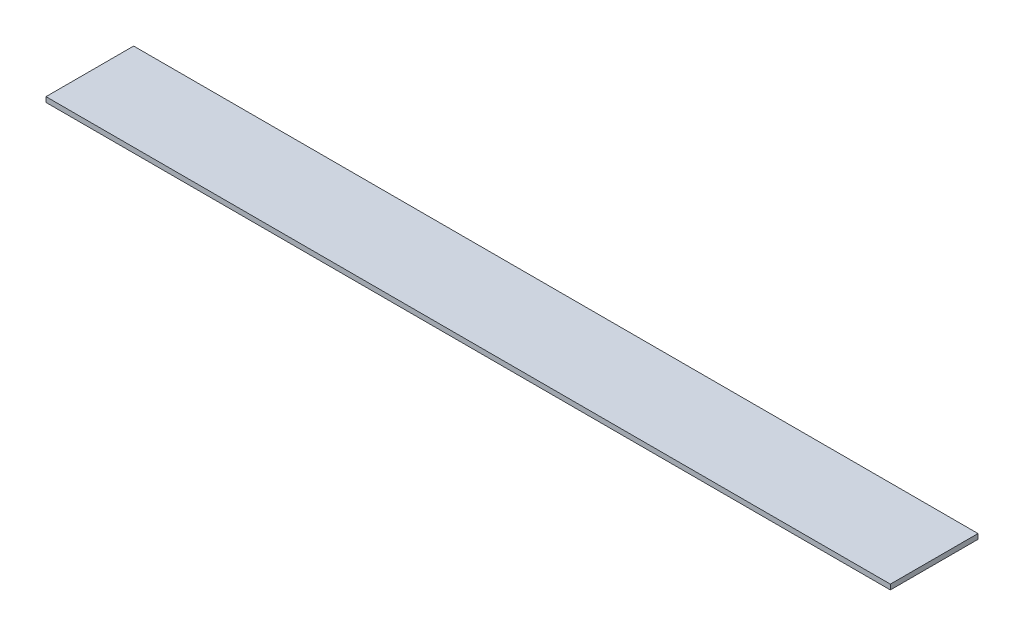
SolidWorks part; units mm, degrees
ref_plane "Front Plane" through (0, 0, 0) normal (0, 0, 1) x (1, 0, 0)
ref_plane "Top Plane" through (0, 0, 0) normal (0, 1, 0) x (1, 0, 0)
ref_plane "Right Plane" through (0, 0, 0) normal (1, 0, 0) x (0, 0, -1)
sketch "Sketch1" plane through (32.3643, 0, 0) normal (1, 0, 0) x (0, 0, -1)
  line L1 (-7.8759, 29.8822) -> (-7.8759, 35.6922) construction
  line L2 (-3.5343, 35.5407) -> (-4.9959, 34.0792)
  line L4 (-4.9959, 34.0792) -> (-4.9959, 33.9551)
  line L5 (-4.9959, 33.9551) -> (-2.3859, 33.9551)
  line L6 (-2.3859, 33.9551) -> (-2.3859, 32.3299)
  line L7 (-2.3859, 32.3299) -> (-5.5407, 29.1751)
  line L8 (-5.5407, 29.1751) -> (-10.2111, 29.1751)
  line L9 (-10.2111, 29.1751) -> (-13.3659, 32.3299)
  line L10 (-13.3659, 32.3299) -> (-13.3659, 33.9551)
  line L11 (-13.3659, 33.9551) -> (-10.7559, 33.9551)
  line L12 (-10.7559, 33.9551) -> (-10.7559, 34.0792)
  line L13 (-10.7559, 34.0792) -> (-12.2174, 35.5407)
  line L14 (-13.3659, 33.9551) -> (-2.9859, 33.9551)
  line L15 (-13.3659, 33.9551) -> (-13.3659, 33.3551)
  line L16 (-13.3659, 33.3551) -> (-2.9859, 33.3551)
  line L17 (-2.9859, 33.9551) -> (-2.9859, 33.3551)
  line L52 (-5.5365, 22.3651) -> (-2.3759, 19.2044)
  line L53 (-2.3759, 19.2044) -> (-2.3759, 17.5651)
  line L54 (-2.3759, 17.5651) -> (-4.9859, 17.5651)
  line L55 (-4.9859, 17.5651) -> (-4.9859, 17.4551)
  line L56 (-4.9859, 17.4551) -> (-3.5273, 15.9964)
  line L57 (-2.9686, 15.7651) -> (0.6241, 15.7651)
  line L58 (2.1241, 17.2651) -> (2.1241, 20.8578)
  line L59 (1.8927, 21.4164) -> (0.4341, 22.8751)
  line L60 (0.4341, 22.8751) -> (0.3241, 22.8751)
  line L61 (0.3241, 22.8751) -> (0.3241, 20.2651)
  line L62 (0.3241, 20.2651) -> (-1.3152, 20.2651)
  line L63 (-1.3152, 20.2651) -> (-4.4759, 23.4257)
  line L64 (-4.4759, 23.4257) -> (-4.4759, 28.1044)
  line L65 (-4.4759, 28.1044) -> (-1.3152, 31.2651)
  line L66 (-1.3152, 31.2651) -> (0.3241, 31.2651)
  line L67 (0.3241, 31.2651) -> (0.3241, 28.6551)
  line L68 (0.3241, 28.6551) -> (0.4341, 28.6551)
  line L69 (0.4341, 28.6551) -> (1.8927, 30.1137)
  line L70 (2.1241, 30.6723) -> (2.1241, 34.2651)
  line L71 (0.6241, 35.7651) -> (-2.9686, 35.7651)
  line L72 (-3.5273, 35.5337) -> (-4.9859, 34.0751)
  line L73 (-4.9859, 34.0751) -> (-4.9859, 33.9651)
  line L74 (-4.9859, 33.9651) -> (-2.3759, 33.9651)
  line L75 (-2.3759, 33.9651) -> (-2.3759, 32.3257)
  line L76 (-2.3759, 32.3257) -> (-5.5365, 29.1651)
  line L77 (-5.5365, 29.1651) -> (-10.2152, 29.1651)
  line L78 (-10.2152, 29.1651) -> (-13.3759, 32.3257)
  line L79 (-13.3759, 32.3257) -> (-13.3759, 33.9651)
  line L80 (-13.3759, 33.9651) -> (-10.7659, 33.9651)
  line L81 (-10.7659, 33.9651) -> (-10.7659, 34.0751)
  line L82 (-10.7659, 34.0751) -> (-12.2245, 35.5337)
  line L83 (-12.7831, 35.7651) -> (-16.3759, 35.7651)
  line L84 (-17.8759, 34.2651) -> (-17.8759, 30.6723)
  line L85 (-17.6445, 30.1137) -> (-16.1859, 28.6551)
  line L86 (-16.1859, 28.6551) -> (-16.0759, 28.6551)
  line L87 (-16.0759, 28.6551) -> (-16.0759, 31.2651)
  line L88 (-16.0759, 31.2651) -> (-14.4365, 31.2651)
  line L89 (-14.4365, 31.2651) -> (-11.2759, 28.1044)
  line L90 (-11.2759, 28.1044) -> (-11.2759, 23.4257)
  line L91 (-11.2759, 23.4257) -> (-14.4365, 20.2651)
  line L92 (-14.4365, 20.2651) -> (-16.0759, 20.2651)
  line L93 (-16.0759, 20.2651) -> (-16.0759, 22.8751)
  line L94 (-16.0759, 22.8751) -> (-16.1859, 22.8751)
  line L95 (-16.1859, 22.8751) -> (-17.6445, 21.4164)
  line L96 (-17.8759, 20.8578) -> (-17.8759, 17.2651)
  line L97 (-16.3759, 15.7651) -> (-12.7831, 15.7651)
  line L98 (-12.2245, 15.9964) -> (-10.7659, 17.4551)
  line L99 (-10.7659, 17.4551) -> (-10.7659, 17.5651)
  line L100 (-10.7659, 17.5651) -> (-13.3759, 17.5651)
  line L101 (-13.3759, 17.5651) -> (-13.3759, 19.2044)
  line L102 (-13.3759, 19.2044) -> (-10.2152, 22.3651)
  line L103 (-10.2152, 22.3651) -> (-5.5365, 22.3651)
  line L104 (-5.5365, 22.3651) -> (-2.3759, 19.2044)
  line L105 (-2.3759, 19.2044) -> (-2.3759, 17.5651)
  line L106 (-2.3759, 17.5651) -> (-4.9859, 17.5651)
  line L107 (-4.9859, 17.5651) -> (-4.9859, 17.4551)
  line L108 (-4.9859, 17.4551) -> (-3.5273, 15.9964)
  line L109 (-2.9686, 15.7651) -> (0.6241, 15.7651)
  line L110 (2.1241, 17.2651) -> (2.1241, 20.8578)
  line L111 (1.8927, 21.4164) -> (0.4341, 22.8751)
  line L112 (0.4341, 22.8751) -> (0.3241, 22.8751)
  line L113 (0.3241, 22.8751) -> (0.3241, 20.2651)
  line L114 (0.3241, 20.2651) -> (-1.3152, 20.2651)
  line L115 (-1.3152, 20.2651) -> (-4.4759, 23.4257)
  line L116 (-4.4759, 23.4257) -> (-4.4759, 28.1044)
  line L117 (-4.4759, 28.1044) -> (-1.3152, 31.2651)
  line L118 (-1.3152, 31.2651) -> (0.3241, 31.2651)
  line L119 (0.3241, 31.2651) -> (0.3241, 28.6551)
  line L120 (0.3241, 28.6551) -> (0.4341, 28.6551)
  line L121 (0.4341, 28.6551) -> (1.8927, 30.1137)
  line L122 (2.1241, 30.6723) -> (2.1241, 34.2651)
  line L123 (0.6241, 35.7651) -> (-2.9686, 35.7651)
  line L124 (-3.5273, 35.5337) -> (-4.9859, 34.0751)
  line L125 (-4.9859, 34.0751) -> (-4.9859, 33.9651)
  line L126 (-4.9859, 33.9651) -> (-2.3759, 33.9651)
  line L127 (-2.3759, 33.9651) -> (-2.3759, 32.3257)
  line L128 (-2.3759, 32.3257) -> (-5.5365, 29.1651)
  line L129 (-5.5365, 29.1651) -> (-10.2152, 29.1651)
  line L130 (-10.2152, 29.1651) -> (-13.3759, 32.3257)
  line L131 (-13.3759, 32.3257) -> (-13.3759, 33.9651)
  line L132 (-13.3759, 33.9651) -> (-10.7659, 33.9651)
  line L133 (-10.7659, 33.9651) -> (-10.7659, 34.0751)
  line L134 (-10.7659, 34.0751) -> (-12.2245, 35.5337)
  line L135 (-12.7831, 35.7651) -> (-16.3759, 35.7651)
  line L136 (-17.8759, 34.2651) -> (-17.8759, 30.6723)
  line L137 (-17.6445, 30.1137) -> (-16.1859, 28.6551)
  line L138 (-16.1859, 28.6551) -> (-16.0759, 28.6551)
  line L139 (-16.0759, 28.6551) -> (-16.0759, 31.2651)
  line L140 (-16.0759, 31.2651) -> (-14.4365, 31.2651)
  line L141 (-14.4365, 31.2651) -> (-11.2759, 28.1044)
  line L142 (-11.2759, 28.1044) -> (-11.2759, 23.4257)
  line L143 (-11.2759, 23.4257) -> (-14.4365, 20.2651)
  line L144 (-14.4365, 20.2651) -> (-16.0759, 20.2651)
  line L145 (-16.0759, 20.2651) -> (-16.0759, 22.8751)
  line L146 (-16.0759, 22.8751) -> (-16.1859, 22.8751)
  line L147 (-16.1859, 22.8751) -> (-17.6445, 21.4164)
  line L148 (-17.8759, 20.8578) -> (-17.8759, 17.2651)
  line L149 (-16.3759, 15.7651) -> (-12.7831, 15.7651)
  line L150 (-12.2245, 15.9964) -> (-10.7659, 17.4551)
  line L151 (-10.7659, 17.4551) -> (-10.7659, 17.5651)
  line L152 (-10.7659, 17.5651) -> (-13.3759, 17.5651)
  line L153 (-13.3759, 17.5651) -> (-13.3759, 19.2044)
  line L154 (-13.3759, 19.2044) -> (-10.2152, 22.3651)
  line L155 (-10.2152, 22.3651) -> (-5.5365, 22.3651)
  arc A12 (-3.5273, 15.9964) -> (-2.9686, 15.7651) centre (-2.9686, 16.5551) ccw
  arc A13 (0.6241, 15.7651) -> (2.1241, 17.2651) centre (0.6241, 17.2651) ccw
  arc A14 (2.1241, 20.8578) -> (1.8927, 21.4164) centre (1.3341, 20.8578) ccw
  arc A15 (1.8927, 30.1137) -> (2.1241, 30.6723) centre (1.3341, 30.6723) ccw
  arc A16 (2.1241, 34.2651) -> (0.6241, 35.7651) centre (0.6241, 34.2651) ccw
  arc A17 (-2.9686, 35.7651) -> (-3.5273, 35.5337) centre (-2.9686, 34.9751) ccw
  arc A18 (-12.2245, 35.5337) -> (-12.7831, 35.7651) centre (-12.7831, 34.9751) ccw
  arc A19 (-16.3759, 35.7651) -> (-17.8759, 34.2651) centre (-16.3759, 34.2651) ccw
  arc A20 (-17.8759, 30.6723) -> (-17.6445, 30.1137) centre (-17.0859, 30.6723) ccw
  arc A21 (-17.6445, 21.4164) -> (-17.8759, 20.8578) centre (-17.0859, 20.8578) ccw
  arc A22 (-17.8759, 17.2651) -> (-16.3759, 15.7651) centre (-16.3759, 17.2651) ccw
  arc A23 (-12.7831, 15.7651) -> (-12.2245, 15.9964) centre (-12.7831, 16.5551) ccw
  arc A24 (-3.5273, 15.9964) -> (-2.9686, 15.7651) centre (-2.9686, 16.5551) ccw
  arc A25 (0.6241, 15.7651) -> (2.1241, 17.2651) centre (0.6241, 17.2651) ccw
  arc A26 (2.1241, 20.8578) -> (1.8927, 21.4164) centre (1.3341, 20.8578) ccw
  arc A27 (1.8927, 30.1137) -> (2.1241, 30.6723) centre (1.3341, 30.6723) ccw
  arc A28 (2.1241, 34.2651) -> (0.6241, 35.7651) centre (0.6241, 34.2651) ccw
  arc A29 (-2.9686, 35.7651) -> (-3.5273, 35.5337) centre (-2.9686, 34.9751) ccw
  arc A30 (-12.2245, 35.5337) -> (-12.7831, 35.7651) centre (-12.7831, 34.9751) ccw
  arc A31 (-16.3759, 35.7651) -> (-17.8759, 34.2651) centre (-16.3759, 34.2651) ccw
  arc A32 (-17.8759, 30.6723) -> (-17.6445, 30.1137) centre (-17.0859, 30.6723) ccw
  arc A33 (-17.6445, 21.4164) -> (-17.8759, 20.8578) centre (-17.0859, 20.8578) ccw
  arc A34 (-17.8759, 17.2651) -> (-16.3759, 15.7651) centre (-16.3759, 17.2651) ccw
  arc A35 (-12.7831, 15.7651) -> (-12.2245, 15.9964) centre (-12.7831, 16.5551) ccw
  dimension "D2" = 0.6
  dimension "D3" = 0.6
  dimension "D1" = 0
  dimension "D5" = 0.01
extrude "Boss-Extrude1" add sketch "Sketch1" along normal blind 100 contours L16 L1 L14 L11 L10 | L1 L16 L17 L5 L14
